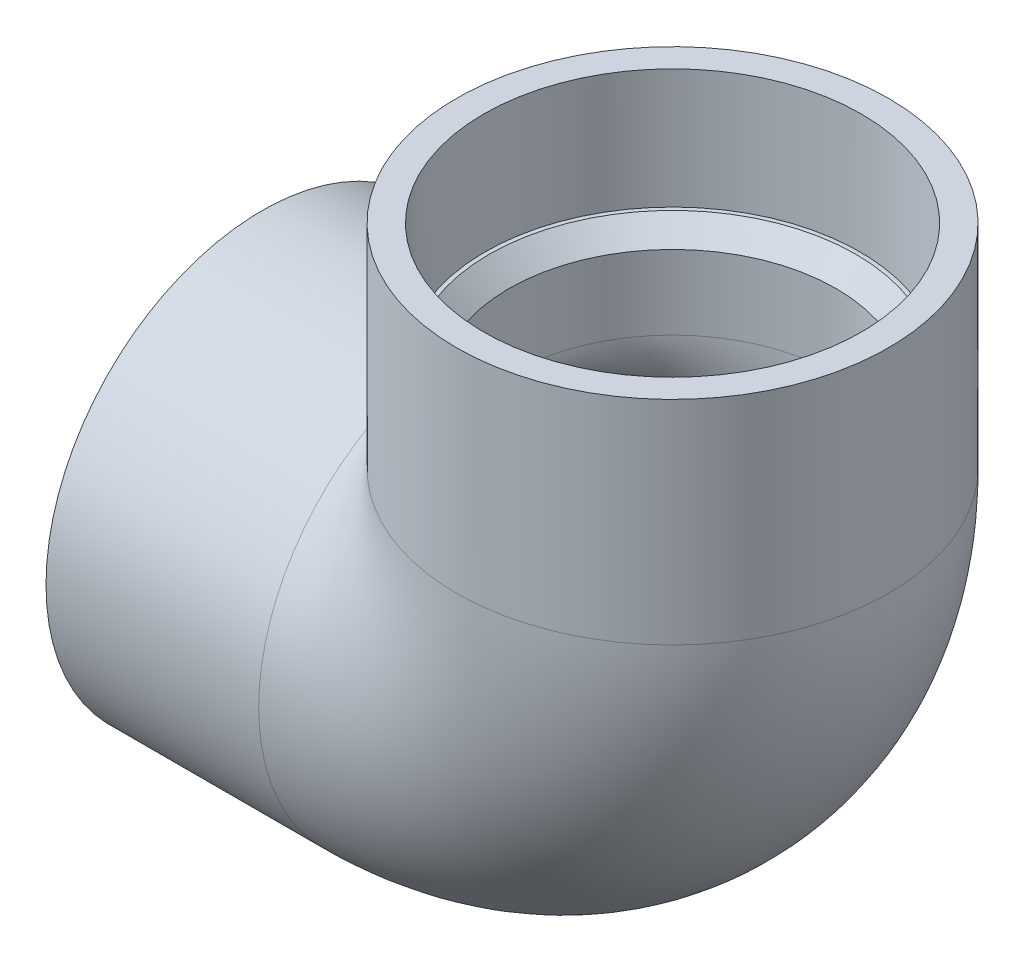
SolidWorks part; units mm, degrees
material "ABS"
ref_plane "Front Plane" through (0, 0, 0) normal (0, 0, 1) x (1, 0, 0)
ref_plane "Top Plane" through (0, 0, 0) normal (0, 1, 0) x (1, 0, 0)
ref_plane "Right Plane" through (0, 0, 0) normal (1, 0, 0) x (0, 0, -1)
sketch "Sketch0" plane through (0, 0, 0) normal (0, 0, 1) x (1, 0, 0)
  line L0 (-65.8813, 0) -> (0, 0) construction
  line L1 (0, 0) -> (0, 65.8813) construction
  line L2 (-31.75, 0) -> (0, 0) construction
  line L3 (0, 0) -> (0, 31.75) construction
  line L4 (-65.8812, 34.671) -> (-65.8812, -34.671) construction
  line L5 (-31.75, 30.0863) -> (-65.8812, 30.3149) construction
  line L6 (-31.75, 30.0863) -> (-31.75, -30.0863) construction
  line L7 (-31.75, -30.0863) -> (-65.8812, -30.3149) construction
  line L8 (-65.8812, 30.3149) -> (-65.8812, -30.3149) construction
  line L9 (-34.671, 65.8813) -> (34.671, 65.8813) construction
  line L10 (-30.3149, 65.8813) -> (30.3149, 65.8813) construction
  line L11 (30.3149, 65.8813) -> (30.0863, 31.75) construction
  line L12 (30.0863, 31.75) -> (-30.0863, 31.75) construction
  line L13 (-30.0863, 31.75) -> (-30.3149, 65.8813) construction
  line L14 (-31.75, 26.2509) -> (-31.75, -26.2509) construction
  line L18 (-26.2509, 31.75) -> (26.2509, 31.75) construction
  dimension "H" = 65.8813
  dimension "G" = 31.75
  dimension "M" = 69.342
  dimension "OD A" = 60.6298
  dimension "OD B" = 60.1726
  dimension "ID" = 52.5018
sketch "Sketch1" plane through (0, 0, 0) normal (0, 0, 1) x (1, 0, 0)
  line L0 (-65.8813, 0) -> (0, 0) construction
  line L1 (-65.8813, 0) -> (0, 0) construction
  line L3 (-65.8812, -34.671) -> (-31.75, -34.671)
  line L4 (-65.8812, -34.671) -> (-65.8812, -30.3149)
  line L5 (-65.8812, -30.3149) -> (-31.75, -30.0863)
  line L6 (-31.75, -34.671) -> (-31.75, -30.0863)
revolve "Revolve1" add sketch "Sketch1" angle 360 about L1
sketch "Sketch2" plane through (0, 0, 0) normal (0, 0, 1) x (1, 0, 0)
  line L0 (30.3149, 65.8813) -> (30.0863, 31.75)
  line L1 (30.0863, 31.75) -> (34.671, 31.75)
  line L2 (34.671, 31.75) -> (34.671, 65.8813)
  line L3 (34.671, 65.8813) -> (30.3149, 65.8813)
  line L4 (0, 0) -> (0, 65.8813) construction
  line L5 (0, 0) -> (0, 65.8813) construction
revolve "Revolve2" add sketch "Sketch2" angle 360 about L5
sketch "Sketch3" plane through (-31.75, 0, 0) normal (1, 0, 0) x (0, 0, -1)
  circle A0 centre (0, 0) radius 26.2509
  circle A1 centre (0, 0) radius 34.671
sketch "Sketch4" plane through (0, 0, 0) normal (0, 0, 1) x (1, 0, 0)
  line L0 (-65.8813, 0) -> (0, 0) construction
  line L1 (0, 0) -> (0, 65.8813) construction
  line L2 (-65.8813, 0) -> (-31.75, 0) construction
  line L3 (0, 31.75) -> (0, 65.8813) construction
  arc A0 (-31.75, 0) -> (0, 31.75) centre (-31.75, 31.75) ccw
sweep "Sweep1" add profiles "Sketch3" path "Sketch4"
sketch "Sketch5" plane through (-31.75, 0, 0) normal (-1, 0, 0) x (0, 0, 1)
  circle A0 centre (0, 0) radius 30.0863 construction
  circle A1 centre (0, 0) radius 26.2509 construction
  circle A2 centre (0, 0) radius 30.0863
  circle A3 centre (0, 0) radius 26.2509
extrude "Boss-Extrude1" add sketch "Sketch5" along normal offset from surface (15.0812 mm away) 19.05 up to face at (-65.8812, 0, 34.671)
sketch "Sketch6" plane through (0, 31.75, 0) normal (0, 1, 0) x (1, 0, 0)
  circle A0 centre (0, 0) radius 26.2509 construction
  circle A1 centre (0, 0) radius 30.0863
  circle A2 centre (0, 0) radius 30.0863
  circle A3 centre (0, 0) radius 26.2509
  dimension "D1" = 0
extrude "Boss-Extrude2" add sketch "Sketch6" along normal offset from surface (15.0812 mm away) 19.05 up to face at (0, 65.8813, -30.3149)
chamfer "Chamfer1" distance 3.175 angle 45 2 edges at (-46.8312, 0, 26.2509) (0, 46.8313, 26.2509)
